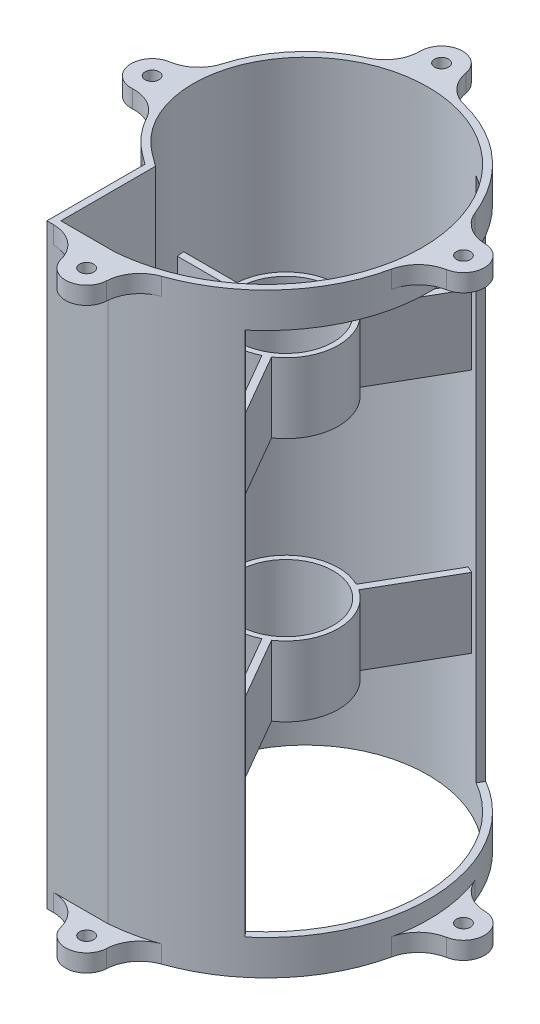
SolidWorks part; units mm, degrees
ref_plane "Front Plane" through (0, 0, 0) normal (0, 0, 1) x (1, 0, 0)
ref_plane "Top Plane" through (0, 0, 0) normal (0, 1, 0) x (1, 0, 0)
ref_plane "Right Plane" through (0, 0, 0) normal (1, 0, 0) x (0, 0, -1)
sketch "Sketch4" plane through (0, 0, 0) normal (0, 1, 0) x (1, 0, 0)
  circle A0 centre (0, 0) radius 27
  dimension "D1" = 54
curve "Helix/Spiral1"
sketch "Sketch5" plane through (0, 0, 0) normal (0, 1, 0) x (1, 0, 0)
  line L0 (-19.0919, -19.0919) -> (-15.3467, -21.875)
  line L1 (-15.3467, -21.875) -> (-15.3467, -48.875)
  line L2 (-15.3467, -48.875) -> (0, -48.875)
  line L3 (-17.3467, -50.875) -> (0.0813, -50.875)
  line L4 (-17.3467, -22.8805) -> (-17.3467, -50.875)
  line L5 (-20.2848, -20.6972) -> (-17.3467, -22.8805)
  circle A0 centre (0, 44.414) radius 2
  circle A1 centre (0, 44.414) radius 6
  arc A2 (5.9121, 45.4375) -> (13.3593, 37.4371) centre (15.7655, 47.1433) ccw
  arc A3 (-5.9997, 44.3518) -> (-11.8204, 35.1632) centre (-15.9991, 44.2482) cw
  circle A4 centre (0, -56.875) radius 2
  circle A5 centre (0, -56.875) radius 6
  arc A6 (12.6771, -48.2201) -> (5.9928, -57.1688) centre (15.9808, -57.6586) ccw
  arc A7 (-5.8095, -58.375) -> (-15.4919, -50.875) centre (-15.4919, -60.875) ccw
  circle A8 centre (-38.1796, 0) radius 2
  circle A9 centre (-38.1796, 0) radius 6
  arc A10 (-39.1278, 5.9246) -> (-31.0965, 13.0387) centre (-40.708, 15.799) ccw
  arc A11 (-37.8576, -5.9913) -> (-28.5532, -11.1676) centre (-37.3208, -15.9769) cw
  circle A12 centre (50.6542, 0) radius 2
  circle A13 centre (50.6542, 0) radius 6
  arc A14 (50.7874, 5.9985) -> (41.7153, 12.3054) centre (51.0093, 15.9961) cw
  arc A15 (51.7349, -5.9019) -> (43.7658, -13.6066) centre (53.5359, -15.7384) ccw
  spline S0 degree 3 poles (-3680.9809, 3340.8545) (425.7388, 239.9226) (42.9993, -85.5028) (-23.7329, -14.7754) (-24.7431, -13.4997) (-26.5442, -10.7574) (-27.3351, -9.2909) (-28.6618, -6.2056) (-29.1975, -4.5868) (-29.9849, -1.2422) (-30.2365, 0.4836) (-30.4346, 3.9917) (-30.3812, 5.7739) (-29.9577, 9.3402) (-29.5876, 11.1242) (-28.529, 14.6371) (-27.8404, 16.366) (-26.1532, 19.7113) (-25.1546, 21.3277) (-22.8664, 24.3921) (-21.5767, 25.8399) (-18.7354, 28.5146) (-17.1837, 29.7413) (-13.857, 31.926) (-12.082, 32.884) (-8.3558, 34.4906) (-6.4048, 35.1391) (-2.3811, 36.0946) (-0.3086, 36.4014) (3.8974, 36.6511) (6.0308, 36.5938) (10.2939, 36.1036) (12.4236, 35.6706) (16.6125, 34.4288) (18.6717, 33.62) (22.6527, 31.6384) (24.5746, 30.4656) (28.2163, 27.7801) (29.9361, 26.2672) (33.1132, 22.9369) (34.5704, 21.1194) (37.1683, 17.2258) (38.3089, 15.1498) (40.2275, 10.7951) (41.0054, 8.5164) (42.1627, 3.8204) (42.542, 1.4031) (42.8775, -3.5) (42.8337, -5.9856) (42.3107, -10.9506) (41.8316, -13.4299) (40.4394, -18.3055) (39.5262, -20.7017) (37.2807, -25.3346) (35.9483, -27.5713) (32.8926, -31.8113) (31.1694, -33.8147) (27.3732, -37.5197) (25.3004, -39.2211) (20.8587, -42.2611) (18.4898, -43.5996) (13.52, -45.8618) (10.9192, -46.7856) (-123.6002, -81.734) (-447.4425, 434.3605) (3794.2506, 3114.1795) knots -1.834704 -1.834704 -1.834704 -1.834704 0.03125 0.03125 0.0625 0.0625 0.09375 0.09375 0.125 0.125 0.15625 0.15625 0.1875 0.1875 0.21875 0.21875 0.25 0.25 0.28125 0.28125 0.3125 0.3125 0.34375 0.34375 0.375 0.375 0.40625 0.40625 0.4375 0.4375 0.46875 0.46875 0.5 0.5 0.53125 0.53125 0.5625 0.5625 0.59375 0.59375 0.625 0.625 0.65625 0.65625 0.6875 0.6875 0.71875 0.71875 0.75 0.75 0.78125 0.78125 0.8125 0.8125 0.84375 0.84375 0.875 0.875 0.90625 0.90625 0.9375 0.9375 0.96875 0.96875 2.505899 2.505899 2.505899 2.505899 only from (-19.0919, -19.0919) to (0, -48.875) construction
  spline S1 degree 3 poles (-19.0919, -19.0919) (-20.3464, -18.1596) (-21.5345, -17.1054) (-23.7329, -14.7754) (-24.7431, -13.4997) (-26.5442, -10.7574) (-27.3351, -9.2909) (-28.6618, -6.2056) (-29.1975, -4.5868) (-29.9849, -1.2422) (-30.2365, 0.4836) (-30.4346, 3.9917) (-30.3812, 5.7739) (-29.9577, 9.3402) (-29.5876, 11.1242) (-28.529, 14.6371) (-27.8404, 16.366) (-26.1532, 19.7113) (-25.1546, 21.3277) (-22.8664, 24.3921) (-21.5767, 25.8399) (-18.7354, 28.5146) (-17.1837, 29.7413) (-13.857, 31.926) (-12.082, 32.884) (-8.3558, 34.4906) (-6.4048, 35.1391) (-2.3811, 36.0946) (-0.3086, 36.4014) (3.8974, 36.6511) (6.0308, 36.5938) (10.2939, 36.1036) (12.4236, 35.6706) (16.6125, 34.4288) (18.6717, 33.62) (22.6527, 31.6384) (24.5746, 30.4656) (28.2163, 27.7801) (29.9361, 26.2672) (33.1132, 22.9369) (34.5704, 21.1194) (37.1683, 17.2258) (38.3089, 15.1498) (40.2275, 10.7951) (41.0054, 8.5164) (42.1627, 3.8204) (42.542, 1.4031) (42.8775, -3.5) (42.8337, -5.9856) (42.3107, -10.9506) (41.8316, -13.4299) (40.4394, -18.3055) (39.5262, -20.7017) (37.2807, -25.3346) (35.9483, -27.5713) (32.8926, -31.8113) (31.1694, -33.8147) (27.3732, -37.5197) (25.3004, -39.2211) (20.8587, -42.2611) (18.4898, -43.5996) (13.52, -45.8618) (10.9192, -46.7856) (5.5586, -48.1783) (2.799, -48.6471) (0, -48.875) knots 0 0 0 0 0.03125 0.03125 0.0625 0.0625 0.09375 0.09375 0.125 0.125 0.15625 0.15625 0.1875 0.1875 0.21875 0.21875 0.25 0.25 0.28125 0.28125 0.3125 0.3125 0.34375 0.34375 0.375 0.375 0.40625 0.40625 0.4375 0.4375 0.46875 0.46875 0.5 0.5 0.53125 0.53125 0.5625 0.5625 0.59375 0.59375 0.625 0.625 0.65625 0.65625 0.6875 0.6875 0.71875 0.71875 0.75 0.75 0.78125 0.78125 0.8125 0.8125 0.84375 0.84375 0.875 0.875 0.90625 0.90625 0.9375 0.9375 0.96875 0.96875 1 1 1 1
  spline S2 degree 1 poles (-20.2848, -20.6972) (0.0813, -50.875) knots 0 0 1 1 construction
  spline S3 degree 3 poles (-20.2848, -20.6972) (-21.6473, -19.6846) (-24.1199, -17.4872) (-26.5211, -14.4824) (-28.1337, -11.952) (-29.6524, -9.1857) (-30.9747, -5.7588) (-32.0568, -1.2493) (-32.4847, 2.8324) (-32.2983, 6.9969) (-31.6775, 11.1651) (-30.5586, 15.0708) (-27.6903, 21.551) (-22.8473, 28.075) (-15.4688, 33.5307) (-9.9133, 36.092) (-5.8109, 37.3695) (-1.6359, 38.2864) (2.6433, 38.6723) (6.9347, 38.5188) (11.2332, 38.0095) (18.4198, 36.2331) (28.4067, 31.0503) (36.1496, 22.9627) (40.6316, 15.139) (42.5539, 10.3068) (43.7079, 6.0613) (44.5367, 1.7594) (44.8838, -2.6369) (44.7438, -7.0291) (44.2824, -11.4267) (43.0338, -17.1589) (39.3588, -26.6492) (32.9672, -35.5342) (24.3015, -42.6231) (18.3948, -45.949) (14.069, -47.7368) (11.3628, -48.6842) (8.2903, -49.5808) (4.4329, -50.4019) (1.5324, -50.7569) (0.0813, -50.875) knots 0 0 0 0 0.031259 0.061044 0.068859 0.084489 0.116573 0.132202 0.163462 0.185157 0.200786 0.232046 0.250075 0.312594 0.355331 0.38605 0.40162 0.417191 0.447065 0.462002 0.476939 0.506813 0.56267 0.625188 0.649397 0.676419 0.68993 0.703734 0.730172 0.743391 0.75661 0.783048 0.812745 0.875264 0.906523 0.937783 0.949936 0.957751 0.969042 0.984672 1.000301 1.000301 1.000301 1.000301
  dimension "D3" = 4
  dimension "D4" = 12
  dimension "D5" = 10
  dimension "D6" = 10
  dimension "D1" = 27
extrude "Boss-Extrude1" add sketch "Sketch5" against normal blind 170 contours S3 L5 L4 L3 L0 S1 L2 L1 region at (-16.1651, 0, 36.8778)
extrude "Boss-Extrude2" add sketch "Sketch5<3>" against normal blind 5 contours A7 A5 L3 | A6 S3 L3 A5 | A5 A4 | A1 S3 A2 | A1 A0 | A3 S3 A1 | A14 S3 A13 | A13 A12 | A13 S3 A15 | A9 A8 | A11 S3 A9 | A9 S3 A10 region at (-7.1008, 0, 52.5626) region at (6.0412, 0, 51.6085) region at (4.1226, 0, 52.7524) region at (-32.5068, 0, 5.4556) region at (-43.9771, 0, 0.618) region at (-33.7619, 0, -6.5387) region at (46.255, 0, 6.6646) region at (47.0994, 0, 4.6212) region at (45.2662, 0, -5.8813) region at (-5.6997, 0, -38.8997) region at (-0.5292, 0, -50.2202) region at (6.6097, 0, -40.0064)
sketch "Sketch5<3>" plane through (0, 0, 0) normal (0, 1, 0) x (1, 0, 0) same geometry as "Sketch5"
extrude "Boss-Extrude3" add sketch "Sketch5<4>" along normal blind 5 from surface contours A7 A5 L3 | A5 A4 | A6 S3 L3 A5 | A3 S3 A1 | A1 A0 | A1 S3 A2 | A13 S3 A15 | A13 A12 | A14 S3 A13 | A9 A8 | A9 S3 A10 | A11 S3 A9 region at (-7.1008, 0, 52.5626) region at (6.0412, 0, 51.6085) region at (4.1226, 0, 52.7524) region at (-32.5068, 0, 5.4556) region at (-43.9771, 0, 0.618) region at (-33.7619, 0, -6.5387) region at (46.255, 0, 6.6646) region at (47.0994, 0, 4.6212) region at (45.2662, 0, -5.8813) region at (-5.6997, 0, -38.8997) region at (-0.5292, 0, -50.2202) region at (6.6097, 0, -40.0064) starting at face at (-16.27, -170, 32.5597)
sketch "Sketch5<4>" plane through (0, 0, 0) normal (0, 1, 0) x (1, 0, 0) same geometry as "Sketch5"
sketch "Sketch6" plane through (0, -170, 0) normal (0, -1, 0) x (1, 0, 0)
  line L0 (0, 0) -> (-30.1249, 0) construction
  line L1 (0, 0) -> (19.2291, -33.3059) construction
  line L2 (0, 0) -> (23.3958, 40.5228) construction
  line L3 (-30.24, -1) -> (-14.9666, -1)
  line L4 (-29.9756, 1) -> (-14.9666, 1)
  line L5 (8.3493, 12.4615) -> (24.2139, 39.9397)
  line L6 (22.5669, 41.087) -> (6.6173, 13.4615)
  line L7 (6.6173, -13.4615) -> (18.3047, -33.7047)
  line L8 (20.1403, -32.884) -> (8.3493, -12.4615)
  circle A0 centre (0, 0) radius 13.5
  circle A1 centre (0, 0) radius 15
  spline S0 degree 3 poles (-1335.8247, -1470.9491) (251.1995, -99.668) (26.267, 67.7688) (-23.7329, 14.7754) (-24.7431, 13.4997) (-26.5442, 10.7574) (-27.3351, 9.2909) (-28.6618, 6.2056) (-29.1975, 4.5868) (-29.9849, 1.2422) (-30.2365, -0.4836) (-30.4346, -3.9917) (-30.3812, -5.7739) (-29.9577, -9.3402) (-29.5876, -11.1242) (-28.529, -14.6371) (-27.8404, -16.366) (-26.1532, -19.7113) (-25.1546, -21.3277) (-22.8664, -24.3921) (-21.5767, -25.8399) (-18.7354, -28.5146) (-17.1837, -29.7413) (-13.857, -31.926) (-12.082, -32.884) (-8.3558, -34.4906) (-6.4048, -35.1391) (-2.3811, -36.0946) (-0.3086, -36.4014) (3.8974, -36.6511) (6.0308, -36.5938) (10.2939, -36.1036) (12.4236, -35.6706) (16.6125, -34.4288) (18.6717, -33.62) (22.6527, -31.6384) (24.5746, -30.4656) (28.2163, -27.7801) (29.9361, -26.2672) (33.1132, -22.9369) (34.5704, -21.1194) (37.1683, -17.2258) (38.3089, -15.1498) (40.2275, -10.7951) (41.0054, -8.5164) (42.1627, -3.8204) (42.542, -1.4031) (42.8775, 3.5) (42.8337, 5.9856) (42.3107, 10.9506) (41.8316, 13.4299) (40.4394, 18.3055) (39.5262, 20.7017) (37.2807, 25.3346) (35.9483, 27.5713) (32.8926, 31.8113) (31.1694, 33.8147) (27.3732, 37.5197) (25.3004, 39.2211) (20.8587, 42.2611) (18.4898, 43.5996) (13.52, 45.8618) (10.9192, 46.7856) (-89.0824, 72.7662) (-291.0287, -201.8404) (1316.0958, -1425.3111) knots -1.359003 -1.359003 -1.359003 -1.359003 0.03125 0.03125 0.0625 0.0625 0.09375 0.09375 0.125 0.125 0.15625 0.15625 0.1875 0.1875 0.21875 0.21875 0.25 0.25 0.28125 0.28125 0.3125 0.3125 0.34375 0.34375 0.375 0.375 0.40625 0.40625 0.4375 0.4375 0.46875 0.46875 0.5 0.5 0.53125 0.53125 0.5625 0.5625 0.59375 0.59375 0.625 0.625 0.65625 0.65625 0.6875 0.6875 0.71875 0.71875 0.75 0.75 0.78125 0.78125 0.8125 0.8125 0.84375 0.84375 0.875 0.875 0.90625 0.90625 0.9375 0.9375 0.96875 0.96875 2.103446 2.103446 2.103446 2.103446 only from (-19.0919, 19.0919) to (0, 48.875) construction
  spline S1 degree 3 poles (-19.0919, 19.0919) (-20.3464, 18.1596) (-21.5345, 17.1054) (-23.7329, 14.7754) (-24.7431, 13.4997) (-26.5442, 10.7574) (-27.3351, 9.2909) (-28.6618, 6.2056) (-29.1975, 4.5868) (-29.9849, 1.2422) (-30.2365, -0.4836) (-30.4346, -3.9917) (-30.3812, -5.7739) (-29.9577, -9.3402) (-29.5876, -11.1242) (-28.529, -14.6371) (-27.8404, -16.366) (-26.1532, -19.7113) (-25.1546, -21.3277) (-22.8664, -24.3921) (-21.5767, -25.8399) (-18.7354, -28.5146) (-17.1837, -29.7413) (-13.857, -31.926) (-12.082, -32.884) (-8.3558, -34.4906) (-6.4048, -35.1391) (-2.3811, -36.0946) (-0.3086, -36.4014) (3.8974, -36.6511) (6.0308, -36.5938) (10.2939, -36.1036) (12.4236, -35.6706) (16.6125, -34.4288) (18.6717, -33.62) (22.6527, -31.6384) (24.5746, -30.4656) (28.2163, -27.7801) (29.9361, -26.2672) (33.1132, -22.9369) (34.5704, -21.1194) (37.1683, -17.2258) (38.3089, -15.1498) (40.2275, -10.7951) (41.0054, -8.5164) (42.1627, -3.8204) (42.542, -1.4031) (42.8775, 3.5) (42.8337, 5.9856) (42.3107, 10.9506) (41.8316, 13.4299) (40.4394, 18.3055) (39.5262, 20.7017) (37.2807, 25.3346) (35.9483, 27.5713) (32.8926, 31.8113) (31.1694, 33.8147) (27.3732, 37.5197) (25.3004, 39.2211) (20.8587, 42.2611) (18.4898, 43.5996) (13.52, 45.8618) (10.9192, 46.7856) (5.5586, 48.1783) (2.799, 48.6471) (0, 48.875) knots 0 0 0 0 0.03125 0.03125 0.0625 0.0625 0.09375 0.09375 0.125 0.125 0.15625 0.15625 0.1875 0.1875 0.21875 0.21875 0.25 0.25 0.28125 0.28125 0.3125 0.3125 0.34375 0.34375 0.375 0.375 0.40625 0.40625 0.4375 0.4375 0.46875 0.46875 0.5 0.5 0.53125 0.53125 0.5625 0.5625 0.59375 0.59375 0.625 0.625 0.65625 0.65625 0.6875 0.6875 0.71875 0.71875 0.75 0.75 0.78125 0.78125 0.8125 0.8125 0.84375 0.84375 0.875 0.875 0.90625 0.90625 0.9375 0.9375 0.96875 0.96875 1 1 1 1
  spline M30 degree 3 poles (0, 48.875) (2.799, 48.6471) (5.5586, 48.1783) (10.9192, 46.7856) (13.52, 45.8618) (18.4898, 43.5996) (20.8587, 42.2611) (25.3004, 39.2211) (27.3732, 37.5197) (31.1694, 33.8147) (32.8926, 31.8113) (35.9483, 27.5713) (37.2807, 25.3346) (39.5262, 20.7017) (40.4394, 18.3055) (41.8316, 13.4299) (42.3107, 10.9506) (42.8337, 5.9856) (42.8775, 3.5) (42.542, -1.4031) (42.1627, -3.8204) (41.0054, -8.5164) (40.2275, -10.7951) (38.3089, -15.1498) (37.1683, -17.2258) (34.5704, -21.1194) (33.1132, -22.9369) (29.9361, -26.2672) (28.2163, -27.7801) (24.5746, -30.4656) (22.6527, -31.6384) (18.6717, -33.62) (16.6125, -34.4288) (12.4236, -35.6706) (10.2939, -36.1036) (6.0308, -36.5938) (3.8974, -36.6511) (-0.3086, -36.4014) (-2.3811, -36.0946) (-6.4048, -35.1391) (-8.3558, -34.4906) (-12.082, -32.884) (-13.857, -31.926) (-17.1837, -29.7413) (-18.7354, -28.5146) (-21.5767, -25.8399) (-22.8664, -24.3921) (-25.1546, -21.3277) (-26.1532, -19.7113) (-27.8404, -16.366) (-28.529, -14.6371) (-29.5876, -11.1242) (-29.9577, -9.3402) (-30.3812, -5.7739) (-30.4346, -3.9917) (-30.2365, -0.4836) (-29.9849, 1.2422) (-29.1975, 4.5868) (-28.6618, 6.2056) (-27.3351, 9.2909) (-26.5442, 10.7574) (-24.7431, 13.4997) (-23.7329, 14.7754) (-21.5345, 17.1054) (-20.3464, 18.1596) (-19.0919, 19.0919) knots 0 0 0 0 0.03125 0.03125 0.0625 0.0625 0.09375 0.09375 0.125 0.125 0.15625 0.15625 0.1875 0.1875 0.21875 0.21875 0.25 0.25 0.28125 0.28125 0.3125 0.3125 0.34375 0.34375 0.375 0.375 0.40625 0.40625 0.4375 0.4375 0.46875 0.46875 0.5 0.5 0.53125 0.53125 0.5625 0.5625 0.59375 0.59375 0.625 0.625 0.65625 0.65625 0.6875 0.6875 0.71875 0.71875 0.75 0.75 0.78125 0.78125 0.8125 0.8125 0.84375 0.84375 0.875 0.875 0.90625 0.90625 0.9375 0.9375 0.96875 0.96875 1 1 1 1
  dimension "D1" = 27
  dimension "D3" = 120
  dimension "D4" = 120
  dimension "D5" = 2
  dimension "D6" = 2
  dimension "D7" = 2
  dimension "D2" = 1.5
extrude "Boss-Extrude4" add sketch "Sketch6" against normal blind 20 from offset 40 contours A1 L4 L3 M30 | A1 L7 L8 M30 | A1 L5 L6 M30 | A1 A0 region at (-22.5542, -170, -0.0029) region at (-14.5757, -170, 0) region at (13.362, -170, -23.1407) region at (15.4435, -170, 26.7507) offset against normal yes
extrude "Boss-Extrude5" add sketch "Sketch6<5>" along normal blind 20 from offset 130 contours A1 L4 L3 M30 | A1 A0 | A1 L7 L8 M30 | A1 L5 L6 M30 region at (-22.5542, -170, -0.0029) region at (-14.5757, -170, 0) region at (13.362, -170, -23.1407) region at (15.4435, -170, 26.7507) offset against normal yes
sketch "Sketch6<5>" plane through (0, -170, 0) normal (0, -1, 0) x (1, 0, 0) same geometry as "Sketch6"
sketch "Sketch7" plane through (0, -170, 0) normal (0, -1, 0) x (1, 0, 0)
  line L0 (24.298, -34.0788) -> (22.7951, -31.4823)
  line L1 (28.5238, 40.3798) -> (26.6021, 38.0761)
  line L2 (20.1403, -32.884) -> (8.3493, -12.4615) construction
  line L3 (8.3493, 12.4615) -> (24.2139, 39.9397) construction
  line L4 (26.6021, 38.0761) -> (28.5238, 40.3798)
  line L5 (22.7951, -31.4823) -> (24.298, -34.0788)
  spline S0 degree 3 poles (-1335.8247, -1470.9491) (251.1995, -99.668) (26.267, 67.7688) (-23.7329, 14.7754) (-24.7431, 13.4997) (-26.5442, 10.7574) (-27.3351, 9.2909) (-28.6618, 6.2056) (-29.1975, 4.5868) (-29.9849, 1.2422) (-30.2365, -0.4836) (-30.4346, -3.9917) (-30.3812, -5.7739) (-29.9577, -9.3402) (-29.5876, -11.1242) (-28.529, -14.6371) (-27.8404, -16.366) (-26.1532, -19.7113) (-25.1546, -21.3277) (-22.8664, -24.3921) (-21.5767, -25.8399) (-18.7354, -28.5146) (-17.1837, -29.7413) (-13.857, -31.926) (-12.082, -32.884) (-8.3558, -34.4906) (-6.4048, -35.1391) (-2.3811, -36.0946) (-0.3086, -36.4014) (3.8974, -36.6511) (6.0308, -36.5938) (10.2939, -36.1036) (12.4236, -35.6706) (16.6125, -34.4288) (18.6717, -33.62) (22.6527, -31.6384) (24.5746, -30.4656) (28.2163, -27.7801) (29.9361, -26.2672) (33.1132, -22.9369) (34.5704, -21.1194) (37.1683, -17.2258) (38.3089, -15.1498) (40.2275, -10.7951) (41.0054, -8.5164) (42.1627, -3.8204) (42.542, -1.4031) (42.8775, 3.5) (42.8337, 5.9856) (42.3107, 10.9506) (41.8316, 13.4299) (40.4394, 18.3055) (39.5262, 20.7017) (37.2807, 25.3346) (35.9483, 27.5713) (32.8926, 31.8113) (31.1694, 33.8147) (27.3732, 37.5197) (25.3004, 39.2211) (20.8587, 42.2611) (18.4898, 43.5996) (13.52, 45.8618) (10.9192, 46.7856) (-89.0824, 72.7662) (-291.0287, -201.8404) (1316.0958, -1425.3111) knots -1.359003 -1.359003 -1.359003 -1.359003 0.03125 0.03125 0.0625 0.0625 0.09375 0.09375 0.125 0.125 0.15625 0.15625 0.1875 0.1875 0.21875 0.21875 0.25 0.25 0.28125 0.28125 0.3125 0.3125 0.34375 0.34375 0.375 0.375 0.40625 0.40625 0.4375 0.4375 0.46875 0.46875 0.5 0.5 0.53125 0.53125 0.5625 0.5625 0.59375 0.59375 0.625 0.625 0.65625 0.65625 0.6875 0.6875 0.71875 0.71875 0.75 0.75 0.78125 0.78125 0.8125 0.8125 0.84375 0.84375 0.875 0.875 0.90625 0.90625 0.9375 0.9375 0.96875 0.96875 2.103446 2.103446 2.103446 2.103446 only from (-19.0919, 19.0919) to (0, 48.875) construction
  spline S1 degree 3 poles (22.7951, -31.4823) (24.0308, -30.7671) (25.2336, -29.9796) (28.2163, -27.7801) (29.9361, -26.2672) (33.1132, -22.9369) (34.5704, -21.1194) (37.1683, -17.2258) (38.3089, -15.1498) (40.2275, -10.7951) (41.0054, -8.5164) (42.1627, -3.8204) (42.542, -1.4031) (42.8775, 3.5) (42.8337, 5.9856) (42.3107, 10.9506) (41.8316, 13.4299) (40.4394, 18.3055) (39.5262, 20.7017) (37.2807, 25.3346) (35.9483, 27.5713) (32.8926, 31.8113) (31.1694, 33.8147) (28.4162, 36.5017) (27.5257, 37.3057) (26.6021, 38.0761) knots 0.542561 0.542561 0.542561 0.542561 0.5625 0.5625 0.59375 0.59375 0.625 0.625 0.65625 0.65625 0.6875 0.6875 0.71875 0.71875 0.75 0.75 0.78125 0.78125 0.8125 0.8125 0.84375 0.84375 0.875 0.875 0.889078 0.889078 0.889078 0.889078
  spline S2 degree 1 poles (24.298, -34.0788) (28.5238, 40.3798) knots 0 0 1 1 construction
  spline S3 degree 3 poles (24.298, -34.0788) (25.7514, -33.2375) (28.5489, -31.3859) (33.7403, -26.9725) (39.2523, -20.2473) (43.8545, -10.6275) (46.081, 0.0312) (45.6993, 11.1406) (42.6271, 22.0561) (37.8803, 30.4502) (32.9002, 36.4206) (30.0287, 39.1244) (28.5238, 40.3798) knots 0.542561 0.542561 0.542561 0.542561 0.564219 0.585876 0.629191 0.672505 0.71582 0.759134 0.802449 0.845764 0.867421 0.889078 0.889078 0.889078 0.889078
  point P12 (0, 0)
  spline M10 degree 3 poles (-20.2848, 20.6972) (-21.6473, 19.6846) (-24.1199, 17.4872) (-26.5211, 14.4824) (-28.1337, 11.952) (-29.6524, 9.1857) (-30.9747, 5.7588) (-32.0568, 1.2493) (-32.4847, -2.8324) (-32.2983, -6.9969) (-31.6775, -11.1651) (-30.5586, -15.0708) (-27.6903, -21.551) (-22.8473, -28.075) (-15.4688, -33.5307) (-9.9133, -36.092) (-5.8109, -37.3695) (-1.6359, -38.2864) (2.6433, -38.6723) (6.9347, -38.5188) (11.2332, -38.0095) (18.4198, -36.2331) (28.4067, -31.0503) (36.1496, -22.9627) (40.6316, -15.139) (42.5539, -10.3068) (43.7079, -6.0613) (44.5367, -1.7594) (44.8838, 2.6369) (44.7438, 7.0291) (44.2824, 11.4267) (43.0338, 17.1589) (39.3588, 26.6492) (32.9672, 35.5342) (24.3015, 42.6231) (18.3948, 45.949) (14.069, 47.7368) (11.3628, 48.6842) (8.2903, 49.5808) (4.4329, 50.4019) (1.5324, 50.7569) (0.0813, 50.875) knots 0 0 0 0 0.031259 0.061044 0.068859 0.084489 0.116573 0.132202 0.163462 0.185157 0.200786 0.232046 0.250075 0.312594 0.355331 0.38605 0.40162 0.417191 0.447065 0.462002 0.476939 0.506813 0.56267 0.625188 0.649397 0.676419 0.68993 0.703734 0.730172 0.743391 0.75661 0.783048 0.812745 0.875264 0.906523 0.937783 0.949936 0.957751 0.969042 0.984672 1.000301 1.000301 1.000301 1.000301 only from (13.3593, -37.4371) to (41.7153, -12.3054)
  spline M14 degree 3 poles (-20.2848, 20.6972) (-21.6473, 19.6846) (-24.1199, 17.4872) (-26.5211, 14.4824) (-28.1337, 11.952) (-29.6524, 9.1857) (-30.9747, 5.7588) (-32.0568, 1.2493) (-32.4847, -2.8324) (-32.2983, -6.9969) (-31.6775, -11.1651) (-30.5586, -15.0708) (-27.6903, -21.551) (-22.8473, -28.075) (-15.4688, -33.5307) (-9.9133, -36.092) (-5.8109, -37.3695) (-1.6359, -38.2864) (2.6433, -38.6723) (6.9347, -38.5188) (11.2332, -38.0095) (18.4198, -36.2331) (28.4067, -31.0503) (36.1496, -22.9627) (40.6316, -15.139) (42.5539, -10.3068) (43.7079, -6.0613) (44.5367, -1.7594) (44.8838, 2.6369) (44.7438, 7.0291) (44.2824, 11.4267) (43.0338, 17.1589) (39.3588, 26.6492) (32.9672, 35.5342) (24.3015, 42.6231) (18.3948, 45.949) (14.069, 47.7368) (11.3628, 48.6842) (8.2903, 49.5808) (4.4329, 50.4019) (1.5324, 50.7569) (0.0813, 50.875) knots 0 0 0 0 0.031259 0.061044 0.068859 0.084489 0.116573 0.132202 0.163462 0.185157 0.200786 0.232046 0.250075 0.312594 0.355331 0.38605 0.40162 0.417191 0.447065 0.462002 0.476939 0.506813 0.56267 0.625188 0.649397 0.676419 0.68993 0.703734 0.730172 0.743391 0.75661 0.783048 0.812745 0.875264 0.906523 0.937783 0.949936 0.957751 0.969042 0.984672 1.000301 1.000301 1.000301 1.000301 only from (43.7658, 13.6066) to (12.6771, 48.2201)
  spline M24 degree 3 poles (0, 48.875) (2.799, 48.6471) (5.5586, 48.1783) (10.9192, 46.7856) (13.52, 45.8618) (18.4898, 43.5996) (20.8587, 42.2611) (25.3004, 39.2211) (27.3732, 37.5197) (31.1694, 33.8147) (32.8926, 31.8113) (35.9483, 27.5713) (37.2807, 25.3346) (39.5262, 20.7017) (40.4394, 18.3055) (41.8316, 13.4299) (42.3107, 10.9506) (42.8337, 5.9856) (42.8775, 3.5) (42.542, -1.4031) (42.1627, -3.8204) (41.0054, -8.5164) (40.2275, -10.7951) (38.3089, -15.1498) (37.1683, -17.2258) (34.5704, -21.1194) (33.1132, -22.9369) (29.9361, -26.2672) (28.2163, -27.7801) (24.5746, -30.4656) (22.6527, -31.6384) (18.6717, -33.62) (16.6125, -34.4288) (12.4236, -35.6706) (10.2939, -36.1036) (6.0308, -36.5938) (3.8974, -36.6511) (-0.3086, -36.4014) (-2.3811, -36.0946) (-6.4048, -35.1391) (-8.3558, -34.4906) (-12.082, -32.884) (-13.857, -31.926) (-17.1837, -29.7413) (-18.7354, -28.5146) (-21.5767, -25.8399) (-22.8664, -24.3921) (-25.1546, -21.3277) (-26.1532, -19.7113) (-27.8404, -16.366) (-28.529, -14.6371) (-29.5876, -11.1242) (-29.9577, -9.3402) (-30.3812, -5.7739) (-30.4346, -3.9917) (-30.2365, -0.4836) (-29.9849, 1.2422) (-29.1975, 4.5868) (-28.6618, 6.2056) (-27.3351, 9.2909) (-26.5442, 10.7574) (-24.7431, 13.4997) (-23.7329, 14.7754) (-21.5345, 17.1054) (-20.3464, 18.1596) (-19.0919, 19.0919) knots 0 0 0 0 0.03125 0.03125 0.0625 0.0625 0.09375 0.09375 0.125 0.125 0.15625 0.15625 0.1875 0.1875 0.21875 0.21875 0.25 0.25 0.28125 0.28125 0.3125 0.3125 0.34375 0.34375 0.375 0.375 0.40625 0.40625 0.4375 0.4375 0.46875 0.46875 0.5 0.5 0.53125 0.53125 0.5625 0.5625 0.59375 0.59375 0.625 0.625 0.65625 0.65625 0.6875 0.6875 0.71875 0.71875 0.75 0.75 0.78125 0.78125 0.8125 0.8125 0.84375 0.84375 0.875 0.875 0.90625 0.90625 0.9375 0.9375 0.96875 0.96875 1 1 1 1
  dimension "D2" = 3
  dimension "D3" = 3
  dimension "D1" = 3
extrude "Cut-Extrude1" cut sketch "Sketch7" against normal blind 150 from offset 10 contours S3 L1 L0 M10 M14 M24 region at (24.2211, -170, -32.3901) offset against normal yes
equation "\"D6@Sketch5\"=\"D5@Sketch5\""
equation "\"D6@Sketch6\"=\"D5@Sketch6\""
equation "\"D7@Sketch6\"=\"D5@Sketch6\""
